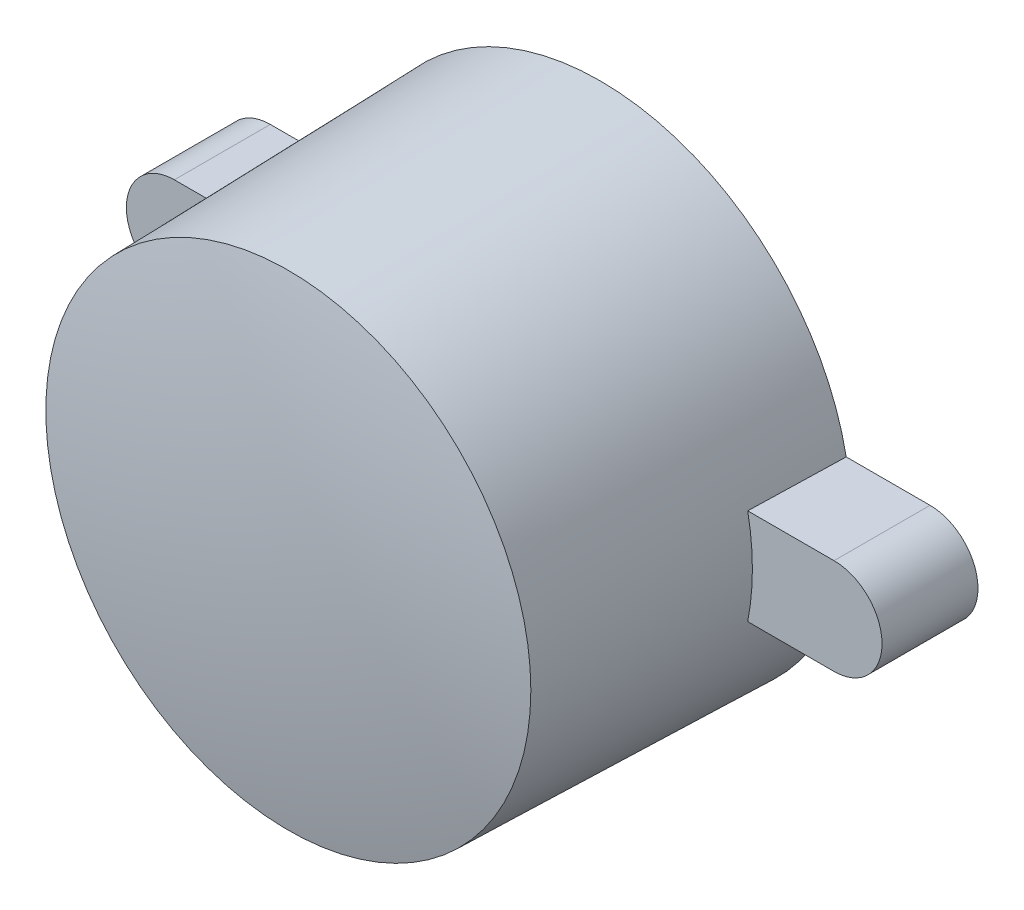
SolidWorks part; units mm, degrees
ref_plane "Front Plane" through (0, 0, 0) normal (0, 0, 1) x (1, 0, 0)
ref_plane "Top Plane" through (0, 0, 0) normal (0, 1, 0) x (1, 0, 0)
ref_plane "Right Plane" through (0, 0, 0) normal (1, 0, 0) x (0, 0, -1)
sketch "Sketch1" plane through (0, 0, 0) normal (0, 0, 1) x (1, 0, 0)
  circle A0 centre (0, 0) radius 5.225
  dimension "D1" = 10.45
extrude "Boss-Extrude1" add sketch "Sketch1" along normal blind 6.5 draft 1.5
dome "Dome1" faces to dome 1 distance 0.5 reverse direction no elliptical dome no face at (5.0548, 0, 6.5) parameters "D1"=0.5
shell "Shell1" thickness 1.75 removed face at (5.225, 0, 0)
sketch "Sketch3" plane through (0, 0, 0) normal (0, 0, -1) x (-1, 0, 0)
  line L0 (-6.875, 1) -> (-3.3274, 1)
  line L1 (-6.875, -1) -> (-3.3274, -1)
  line L2 (-6.875, 1) -> (-6.875, -1) construction
  line L3 (6.875, 1) -> (6.875, -1) construction
  line L4 (-6.875, 0) -> (6.875, 0) construction
  line L5 (3.3274, 1) -> (6.875, 1)
  line L6 (3.3274, -1) -> (6.875, -1)
  arc A0 (-6.875, 1) -> (-6.875, -1) centre (-6.875, 0) ccw
  arc A1 (6.875, -1) -> (6.875, 1) centre (6.875, 0) ccw
  circle A2 centre (0, 0) radius 3.4744 construction
  arc A3 (-3.3274, 1) -> (-3.3274, -1) centre (0, 0) ccw
  arc A4 (3.3274, -1) -> (3.3274, 1) centre (0, 0) ccw
  point P2 (0, 0)
  dimension "D1" = 2
  dimension "D2" = 13.75
extrude "Boss-Extrude2" add sketch "Sketch3" against normal blind 2
